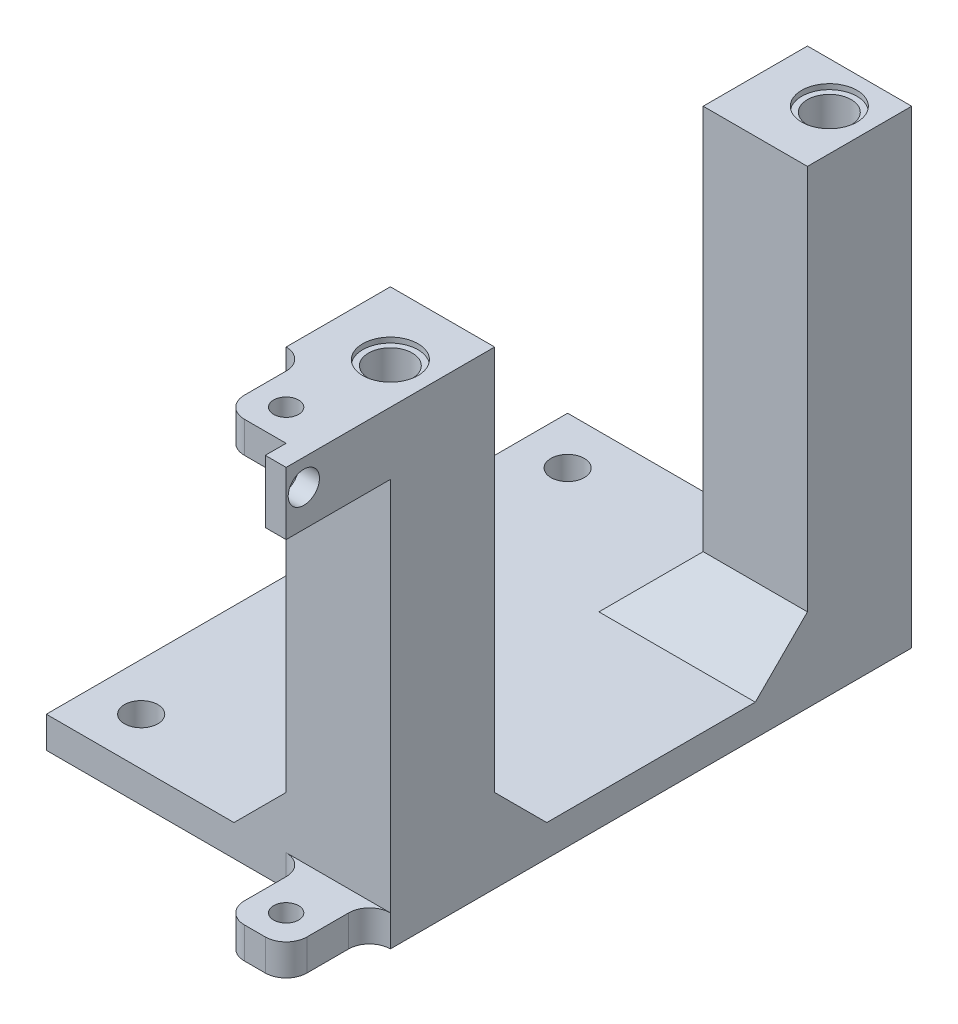
SolidWorks part; units mm, degrees
ref_plane "Front Plane" through (0, 0, 0) normal (0, 0, 1) x (1, 0, 0)
ref_plane "Top Plane" through (0, 0, 0) normal (0, 1, 0) x (1, 0, 0)
ref_plane "Right Plane" through (0, 0, 0) normal (1, 0, 0) x (0, 0, -1)
sketch "Sketch1" plane through (0, 0, 0) normal (0, 1, 0) x (1, 0, 0)
  line L1 (-6.5124, 9.686) -> (1.4876, 9.686)
  line L2 (-6.5124, 9.686) -> (-6.5124, -40.314)
  line L3 (-6.5124, -40.314) -> (1.4876, -40.314)
  line L4 (1.4876, 9.686) -> (1.4876, -40.314)
  line L5 (1.4876, 9.686) -> (26.4876, 9.686)
  line L6 (1.4876, 9.686) -> (1.4876, -40.314)
  line L7 (1.4876, -40.314) -> (26.4876, -40.314)
  line L8 (26.4876, 9.686) -> (26.4876, -40.314)
  circle A0 centre (-1.9624, -35.764) radius 1.6
  circle A1 centre (-1.9624, 5.136) radius 1.6
  dimension "D4" = 3.2
  dimension "D5" = 3.2
  dimension "D6" = 4.55
  dimension "D7" = 4.55
  dimension "D8" = 4.55
  dimension "D9" = 4.55
  dimension "D1" = 8
  dimension "D2" = 50
  dimension "D3" = 25
extrude "Boss-Extrude1" add sketch "Sketch1" along normal blind 3 contours A1 | A0 | L5 L8 L7 L3 L2 L1
sketch "Sketch2" plane through (0, 3, 0) normal (0, 1, 0) x (1, 0, 0)
  line L1 (26.4876, -40.314) -> (16.4876, -40.314)
  line L2 (26.4876, -40.314) -> (26.4876, -30.314)
  line L3 (26.4876, -30.314) -> (16.4876, -30.314)
  line L4 (16.4876, -40.314) -> (16.4876, -30.314)
  line L5 (26.4876, 9.686) -> (16.4876, 9.686)
  line L6 (26.4876, 9.686) -> (26.4876, -0.314)
  line L7 (26.4876, -0.314) -> (16.4876, -0.314)
  line L8 (16.4876, 9.686) -> (16.4876, -0.314)
  dimension "D1" = 10
  dimension "D2" = 10
  dimension "D3" = 10
  dimension "D4" = 10
extrude "Boss-Extrude2" add sketch "Sketch2" along normal blind 42
chamfer "Chamfer1" distance 5 angle 45 4 edges at (16.4876, 3, -4.686) (21.4876, 3, 0.314) (16.4876, 3, 35.314) (21.4876, 3, 30.314)
ref_plane "Plane1" through (0, 45, 0) normal (0, 1, 0) x (1, 0, 0)
sketch "Sketch3" plane through (0, 45, 0) normal (0, 1, 0) x (1, 0, 0)
  line L0 (26.4876, -40.314) -> (26.4876, -30.314) construction
  line L1 (16.4876, -40.314) -> (26.4876, -40.314) construction
  line L2 (26.4876, -0.314) -> (26.4876, 9.686) construction
  line L3 (26.4876, 9.686) -> (16.4876, 9.686) construction
  circle A0 centre (22.5376, -36.364) radius 2.1
  circle A1 centre (22.5376, 5.736) radius 2.1
  dimension "D1" = 4.2
  dimension "D3" = 3.95
  dimension "D4" = 4.2
  dimension "D6" = 3.95
  dimension "D2" = 3.95
  dimension "D5" = 3.95
extrude "Cut-Extrude1" cut sketch "Sketch3" against normal blind 52
sketch "Sketch4" plane through (0, 45, 0) normal (0, 1, 0) x (1, 0, 0)
  circle A0 centre (22.5376, -36.364) radius 2.65
  circle A1 centre (22.5376, 5.736) radius 2.65
  dimension "D1" = 5.3
  dimension "D2" = 5.3
extrude "Cut-Extrude2" cut sketch "Sketch4" against normal blind 0.5
ref_plane "Plane2" through (0, 22.5, 0) normal (0, -1, 0) x (-1, 0, 0)
mirror "Mirror1" about plane through (0, 22.5, 0) normal (0, -1, 0) of "Cut-Extrude2"
sketch "Sketch5" plane through (0, 0, -9.686) normal (0, 0, -1) x (-1, 0, 0)
  line L0 (-22.4876, 36.5) -> (-17.9876, 36.5) construction
  line L1 (-18.2876, 36.2) -> (-22.2399, 36.2)
  line L2 (-18.2876, 36.2) -> (-18.2876, 31.6868)
  line L3 (-18.2876, 31.6868) -> (-22.2399, 31.6868)
  line L4 (-22.2399, 36.2) -> (-22.2399, 31.6868)
  line L5 (-17.9876, 32.25) -> (-17.9876, 37) construction
  dimension "D1" = 0.3
  dimension "D2" = 0.3
sketch "Sketch11" plane through (0, 0, 40.314) normal (0, 0, 1) x (1, 0, 0)
  line L0 (16.4876, 45) -> (26.4876, 45) construction
  line L1 (18.4876, 45) -> (24.4876, 45)
  line L2 (18.4876, 45) -> (18.4876, 42)
  line L3 (18.4876, 42) -> (24.4876, 42)
  line L4 (24.4876, 45) -> (24.4876, 42)
  line L5 (-6.5124, 0) -> (26.4876, 0) construction
  line L6 (18.4876, 0) -> (24.4876, 0)
  line L7 (18.4876, 0) -> (18.4876, 3)
  line L8 (18.4876, 3) -> (24.4876, 3)
  line L9 (24.4876, 0) -> (24.4876, 3)
  line L10 (21.4876, 8) -> (21.4876, 0) construction
  line L11 (21.4876, 8) -> (21.4876, 45) construction
  line L13 (-6.5124, 3) -> (11.4876, 3) construction
  line L14 (16.4876, 8) -> (26.4876, 8) construction
  line L15 (26.4876, 8) -> (39.3241, 4.4212) construction
  line L16 (39.3241, 4.4212) -> (39.5028, 4.4212) construction
  dimension "D1" = 3
  dimension "D2" = 3
  dimension "D3" = 3
  dimension "D4" = 3
  dimension "D5" = 3
extrude "Boss-Extrude7" add sketch "Sketch11" along normal blind 8
sketch "Sketch12" plane through (0, 0, 0) normal (0, -1, 0) x (1, 0, 0)
  line L0 (24.4876, 48.314) -> (24.4876, 40.314) construction
  line L1 (18.4876, 48.314) -> (24.4876, 48.314) construction
  line L2 (18.4876, 48.314) -> (18.4876, 42.314) construction
  line L3 (18.4876, 42.314) -> (24.4876, 42.314) construction
  line L4 (24.4876, 48.314) -> (24.4876, 42.314) construction
  line L5 (18.4876, 48.314) -> (24.4876, 42.314) construction
  line L6 (18.4876, 42.314) -> (24.4876, 48.314) construction
  circle A0 centre (21.4876, 45.314) radius 1.2
  point P494 (21.4876, 45.314)
  dimension "D1" = 2.4
  dimension "D2" = 6
extrude "Cut-Extrude5" cut sketch "Sketch12" against normal through all
fillet "Fillet1" radius 2 6 edges at (18.4876, 43.5, 40.314) (18.4876, 43.5, 48.314) (24.4876, 1.5, 48.314) (18.4876, 1.5, 48.314) (18.4876, 1.5, 40.314) (24.4876, 1.5, 40.314)
sketch "Sketch13" plane through (0, 0, 40.314) normal (0, 0, 1) x (1, 0, 0)
  line L0 (26.4876, 45) -> (26.4876, 3) construction
  line L1 (24.4876, 45) -> (26.4876, 45)
  line L2 (24.4876, 45) -> (24.4876, 42)
  line L3 (24.4876, 42) -> (26.4876, 42)
  line L4 (26.4876, 45) -> (26.4876, 42)
  line L5 (16.4876, 42) -> (24.4876, 42) construction
extrude "Boss-Extrude8" add sketch "Sketch13" along normal blind 10
sketch "Sketch14" plane through (0, 42, 0) normal (0, -1, 0) x (1, 0, 0)
  line L0 (16.4876, 40.314) -> (26.4876, 40.314) construction
  line L1 (26.4876, 50.314) -> (24.4876, 50.314)
  line L2 (26.4876, 50.314) -> (26.4876, 40.314)
  line L3 (26.4876, 40.314) -> (24.4876, 40.314)
  line L4 (24.4876, 50.314) -> (24.4876, 40.314)
  line L5 (24.4876, 50.314) -> (24.4876, 48.314) construction
extrude "Boss-Extrude9" add sketch "Sketch14" along normal blind 3
sketch "Sketch15" plane through (26.4876, 0, 0) normal (1, 0, 0) x (0, 0, -1)
  circle A0 centre (-48.614, 42.5) radius 1.5
  dimension "D1" = 3
extrude "Cut-Extrude6" cut sketch "Sketch15" against normal blind 3
